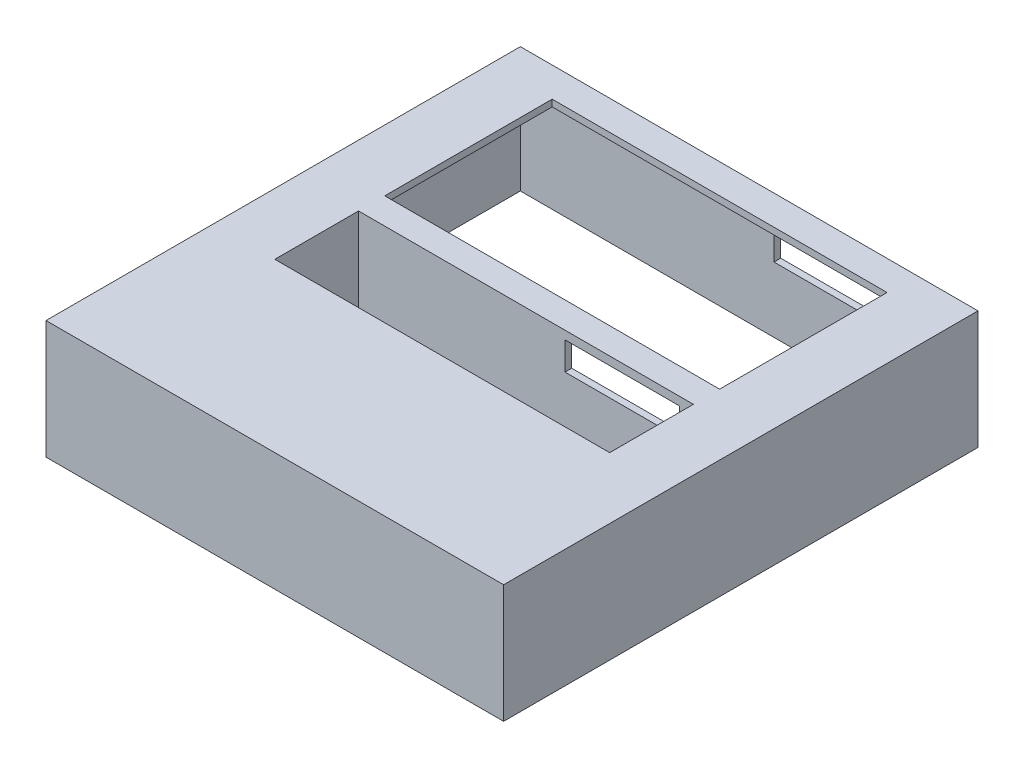
SolidWorks part; units mm, degrees
ref_plane "Front Plane" through (0, 0, 0) normal (0, 0, 1) x (1, 0, 0)
ref_plane "Top Plane" through (0, 0, 0) normal (0, 1, 0) x (1, 0, 0)
ref_plane "Right Plane" through (0, 0, 0) normal (1, 0, 0) x (0, 0, -1)
sketch "Sketch1" plane through (0, 0, 0) normal (0, 1, 0) x (1, 0, 0)
  line L1 (0, 0) -> (82, 0)
  line L2 (0, 0) -> (0, 85)
  line L3 (0, 85) -> (82, 85)
  line L4 (82, 0) -> (82, 85)
  dimension "D1" = 82
  dimension "D2" = 85
extrude "Boss-Extrude1" add sketch "Sketch1" along normal blind 1.2
sketch "Sketch2" plane through (0, 1.2, 0) normal (0, 1, 0) x (1, 0, 0)
  line L0 (0, 83.7) -> (82, 83.7) construction
  line L1 (0, 85) -> (0, 0) construction
  line L2 (82, 0) -> (82, 85) construction
  line L3 (0, 79.7) -> (82, 79.7) construction
  line L4 (0, 49.7) -> (82, 49.7) construction
  line L5 (0, 46.2) -> (82, 46.2) construction
  line L7 (0, 45) -> (82, 45) construction
  line L8 (0, 0) -> (82, 0) construction
  line L10 (11, 79.7) -> (71, 79.7)
  line L11 (11, 79.7) -> (11, 49.7)
  line L12 (11, 49.7) -> (71, 49.7)
  line L13 (71, 79.7) -> (71, 49.7)
  dimension "D1" = 45
  dimension "D2" = 4
  dimension "D3" = 30
  dimension "D4" = 3.5
  dimension "D5" = 1.2
  dimension "D6" = 11
  dimension "D7" = 11
extrude "Cut-Extrude1" cut sketch "Sketch2" against normal blind 2
sketch "Sketch3" plane through (0, 1.2, 0) normal (0, 1, 0) x (1, 0, 0)
  line L0 (11, 85) -> (11, 0) construction
  line L1 (82, 85) -> (0, 85) construction
  line L2 (0, 0) -> (82, 0) construction
  line L3 (71, 85) -> (71, 0) construction
  line L4 (0, 85) -> (0, 0) construction
  line L5 (82, 0) -> (82, 85) construction
  line L7 (11, 45) -> (71, 45)
  line L8 (11, 45) -> (11, 30)
  line L9 (11, 30) -> (71, 30)
  line L10 (71, 45) -> (71, 30)
  dimension "D1" = 11
  dimension "D2" = 11
  dimension "D3" = 30
  dimension "D4" = 15
extrude "Cut-Extrude2" cut sketch "Sketch3" against normal blind 2
sketch "Sketch4" plane through (0, 0, 0) normal (0, -1, 0) x (1, 0, 0)
  line L0 (82, -1.2) -> (0, -1.2) construction
  line L1 (82, 0) -> (82, -85) construction
  line L2 (0, -85) -> (0, 0) construction
  line L3 (1.2, -85) -> (1.2, 0) construction
  line L4 (82, -85) -> (0, -85) construction
  line L5 (0, 0) -> (82, 0) construction
  line L6 (82, -83.8) -> (0, -83.8) construction
  line L7 (80.8, -85) -> (80.8, 0) construction
  line L8 (80.8, -83.8) -> (1.2, -83.8)
  line L9 (1.2, -83.8) -> (1.2, -1.2)
  line L10 (1.2, -1.2) -> (80.8, -1.2)
  line L11 (80.8, -1.2) -> (80.8, -83.8)
  line M13 (0, 0) -> (0, -85)
  line M14 (0, -85) -> (82, -85)
  line M15 (82, -85) -> (82, 0)
  line M16 (82, 0) -> (0, 0)
  dimension "D1" = 1.2
  dimension "D2" = 1.2
  dimension "D3" = 1.2
  dimension "D4" = 1.2
extrude "Boss-Extrude2" add sketch "Sketch4" along normal blind 20 contours L10 L11 L8 L9 M16 M13 M14 M15 region at (41, 0, -1.1811)
sketch "Sketch5" plane through (0, 0, 0) normal (0, -1, 0) x (1, 0, 0)
  line L0 (71, -45) -> (71, -30) construction
  line L1 (72.2, -46.2) -> (9.8, -46.2)
  line L2 (72.2, -46.2) -> (72.2, -28.8)
  line L3 (72.2, -28.8) -> (9.8, -28.8)
  line L4 (9.8, -46.2) -> (9.8, -28.8)
  line L5 (11, -30) -> (11, -45) construction
  line L6 (11, -45) -> (71, -45) construction
  line L7 (71, -30) -> (11, -30) construction
  line M9 (11, -45) -> (11, -30)
  line M10 (11, -30) -> (71, -30)
  line M11 (71, -30) -> (71, -45)
  line M12 (71, -45) -> (11, -45)
  dimension "D1" = 1.2
  dimension "D2" = 1.2
  dimension "D3" = 1.2
  dimension "D4" = 1.2
extrude "Boss-Extrude4" add sketch "Sketch5" along normal blind 20 contours M9 M12 M11 M10 | L2 L3 L4 L1 region at (41, 0, -37.5)
sketch "Sketch10" plane through (0, 0, 0) normal (0, -1, 0) x (1, 0, 0)
  line L0 (9.2, -28.8) -> (9.2, -1.2) construction
  line L1 (72.2, -28.8) -> (9.8, -28.8) construction
  line L2 (1.2, -1.2) -> (80.8, -1.2) construction
  line L3 (1.2, -83.8) -> (1.2, -1.2) construction
  line L5 (9.2, -28.8) -> (10.4, -28.8)
  line L6 (9.2, -28.8) -> (9.2, -25)
  line L7 (9.2, -25) -> (10.4, -25)
  line L8 (10.4, -28.8) -> (10.4, -25)
  point P8 (11.3338, -25)
  dimension "D1" = 8
  dimension "D2" = 3.8
  dimension "D3" = 1.2
extrude "Boss-Extrude5" add sketch "Sketch10" along normal blind 20
sketch "Sketch11" plane through (0, 0, 0) normal (-1, 0, 0) x (0, 0, 1)
  line L0 (-22, -20) -> (-22, 1.2) construction
  line L1 (0, -20) -> (-85, -20) construction
  line L2 (-85, 1.2) -> (0, 1.2) construction
  line L3 (0, 1.2) -> (0, -20) construction
  line L5 (-22, -15) -> (-27, -15)
  line L6 (-22, -15) -> (-22, -3.8)
  line L7 (-22, -3.8) -> (-27, -3.8)
  line L8 (-27, -15) -> (-27, -3.8)
  dimension "D1" = 22
  dimension "D2" = 5
  dimension "D3" = 5
  dimension "D4" = 5
extrude "Cut-Extrude3" cut sketch "Sketch11" against normal blind 1.5
sketch "Sketch12" plane through (0, 0, -85) normal (0, 0, -1) x (-1, 0, 0)
  line L0 (-68.15, -20) -> (-68.15, 1.2) construction
  line L1 (0, -20) -> (-82, -20) construction
  line L2 (-82, 1.2) -> (0, 1.2) construction
  line L3 (-46.65, -20) -> (-46.65, 1.2) construction
  line L4 (-82, 1.2) -> (-82, -20) construction
  line L5 (-68.15, -8.3) -> (-46.65, -8.3)
  line L6 (-68.15, -8.3) -> (-68.15, -0.3)
  line L7 (-68.15, -0.3) -> (-46.65, -0.3)
  line L8 (-46.65, -8.3) -> (-46.65, -0.3)
  dimension "D1" = 13.85
  dimension "D2" = 21.5
  dimension "D3" = 1.5
  dimension "D4" = 8
extrude "Cut-Extrude4" cut sketch "Sketch12" against normal blind 1.5
sketch "Sketch15" plane through (0, 0, -45) normal (0, 0, 1) x (1, 0, 0)
  line L0 (68.5, 1.2) -> (68.5, -20) construction
  line L1 (71, 1.2) -> (11, 1.2) construction
  line L2 (71, -20) -> (11, -20) construction
  line L3 (48, 1.2) -> (48, -20) construction
  line L4 (71, -20) -> (71, 1.2) construction
  line L5 (68.5, -0.3) -> (48, -0.3)
  line L6 (68.5, -0.3) -> (68.5, -5.3)
  line L7 (68.5, -5.3) -> (48, -5.3)
  line L8 (48, -0.3) -> (48, -5.3)
  dimension "D1" = 2.5
  dimension "D2" = 20.5
  dimension "D3" = 1.5
  dimension "D4" = 5
extrude "Cut-Extrude5" cut sketch "Sketch15" against normal blind 1.5 contours L8 L7 L6 L5
